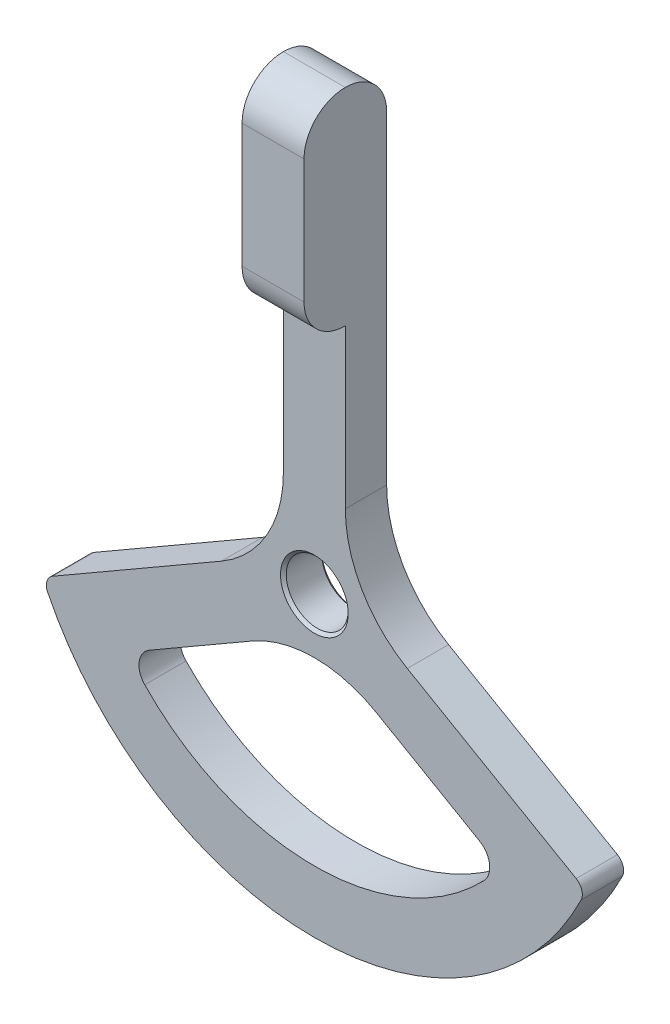
SolidWorks part; units mm, degrees
material "ABS"
ref_plane "정면" through (0, 0, 0) normal (0, 0, 1) x (1, 0, 0)
ref_plane "윗면" through (0, 0, 0) normal (0, 1, 0) x (1, 0, 0)
ref_plane "우측면" through (0, 0, 0) normal (1, 0, 0) x (0, 0, -1)
sketch "스케치2" plane through (0, 0, 0) normal (0, 0, 1) x (1, 0, 0)
  line L0 (0, 0) -> (0, 110) construction
  line L1 (0, 0) -> (-62.3538, -36) construction
  line L2 (0, 0) -> (62.3538, -36) construction
  line L3 (-65.7646, -29.309) -> (-7.5, 4.3301)
  line L4 (-7.5, 4.3301) -> (-7.5, 110)
  line L5 (65.7646, -29.309) -> (7.5, 4.3301)
  line L6 (7.5, 4.3301) -> (7.5, 110)
  line L7 (45.1843, -34.7474) -> (0, -8.6603)
  line L8 (-45.1843, -34.7474) -> (0, -8.6603)
  line L9 (0, 110) -> (-7.5, 110)
  line L10 (-45.1843, -34.7474) -> (0, -8.6603) construction
  line L11 (45.1843, -34.7474) -> (0, -8.6603) construction
  line L12 (0, 110) -> (7.5, 110)
  circle A0 centre (0, 0) radius 72 construction
  arc A1 (-65.7646, -29.309) -> (65.7646, -29.309) centre (0, 0) ccw
  arc A2 (-45.1843, -34.7474) -> (45.1843, -34.7474) centre (0, 0) ccw
  dimension "D1" = 144
  dimension "D6" = 110
  dimension "D3" = 7.5
  dimension "D4" = 7.5
  dimension "D7" = 7.5
  dimension "D8" = 15
  dimension "D9" = 60
  dimension "D10" = 60
  dimension "D11" = 7.5
  dimension "D5" = 15
extrude "보스-돌출1" add sketch "스케치2" along normal mid plane 10
fillet "필렛1" radius 30 3 edges at (-7.5, 4.3301, 0) (7.5, 4.3301, 0) (0, -8.6603, 0)
fillet "필렛2" radius 5 2 edges at (-45.1843, -34.7474, 0) (45.1843, -34.7474, 0)
sketch "스케치9" plane through (7.5, 0, 0) normal (1, 0, 0) x (0, 0, -1)
  line L0 (5, 21.6506) -> (5, 110) construction
  line L1 (-5, 110) -> (-15, 110)
  line L2 (-5, 110) -> (-5, 60)
  line L3 (-5, 60) -> (-15, 60)
  line L4 (-15, 110) -> (-15, 60)
  dimension "D1" = 20
  dimension "D2" = 50
extrude "보스-돌출3" add sketch "스케치9" against normal up to surface (15 mm away) up to face at (-7.5, 65.8253, 0)
fillet "필렛4" radius 10 3 edges at (0, 110, -5) (0, 110, 15) (0, 60, 15)
sketch "스케치10" plane through (0, 0, 5) normal (0, 0, 1) x (1, 0, 0)
  circle A0 centre (0, 0) radius 7.5
  dimension "D1" = 15
extrude "컷-돌출1" cut sketch "스케치10" against normal up to next
chamfer "모따기1" distance 0.7 angle 45 2 edges at (7.5, 0, 5) (7.5, 0, -5)
fillet "필렛5" radius 3 2 edges at (65.7646, -29.309, 0) (-65.7646, -29.309, 0)
